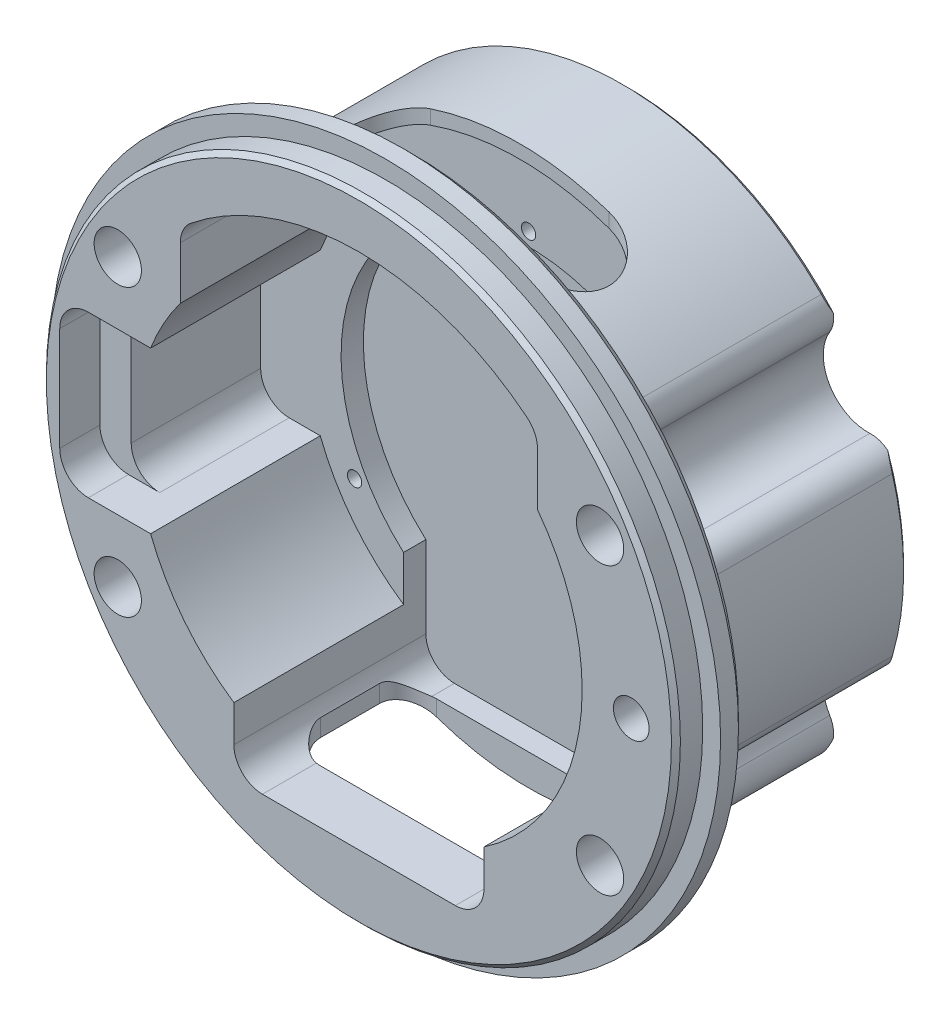
SolidWorks part; units mm, degrees
note: '?' marks a value the reader was unsure of.
material "6061-T6"
ref_plane "Plan de face" through (0, 0, 0) normal (0, 0, 1) x (1, 0, 0)
ref_plane "Plan de dessus" through (0, 0, 0) normal (0, 1, 0) x (1, 0, 0)
ref_plane "Plan de droite" through (0, 0, 0) normal (1, 0, 0) x (0, 0, -1)
ref_axis "X" through (-120.0359, 0, 0) along (1, 0, 0)?
ref_axis "Y" through (0, -123.4668, 0) along (0, 1, 0)?
ref_axis "Z" through (0, 0, 127.7992) along (0, 0, -1)?
sketch "Sketch1" plane through (0, 0, 0) normal (0, 0, 1) x (1, 0, 0)
  circle A0 centre (0, 0) radius 37.5
  dimension "D1" = 75
extrude "Boss-Extrude1" add sketch "Sketch1" along normal blind 27
sketch "Sketch2" plane through (0, 0, 27) normal (0, 0, 1) x (1, 0, 0)
  circle A0 centre (0, 0) radius 35.5
  dimension "D1" = 71
extrude "Boss-Extrude2" add sketch "Sketch2" along normal blind 3
sketch "Sketch13" plane through (0, 0, 0) normal (0, 0, -1) x (-1, 0, 0)
  circle A0 centre (0, 0) radius 31.5
  dimension "D1" = 63
extrude "Cut-Extrude2" cut sketch "Sketch13" against normal offset from surface (24 mm away) 3 flip side to cut up to face at (35.5, 0, 27)
hole_wizard "CBORE for M5 SHCS1" positions "Sketch3" profile "Sketch4" counterbore size "M5" standard "ANSI Metric" end condition through all
sketch "Sketch3" plane through (0, 0, 0) normal (0, 0, -1) x (-1, 0, 0)
  line L0 (0, 0) -> (47.1318, 0) construction
  line L1 (0, 0) -> (0, 39.9387) construction
  point P6 (-27, 16)
  point P8 (27, 16)
  point P9 (27, -16)
  point P10 (-27, -16)
  dimension "D1" = 54
  dimension "D2" = 32
sketch "Sketch4" plane through (27, -16, 0) normal (1, 0, 0) x (0, 1, 0)
  line L0 (0, 0) -> (0, 30)
  line L1 (0, 30) -> (2.65, 30)
  line L3 (2.65, 30) -> (2.65, 24)
  line L4 (2.65, 24) -> (5, 24)
  line L5 (5, 24) -> (5, 0)
  line L7 (5, 0) -> (0, 0)
  line L11 (0, -6.35) -> (0, 107.95) construction
  dimension "Thru Hole Dia." = 5.3
  dimension "Thru Hole Depth" = 30
  dimension "C'Bore Dia." = 10
  dimension "C'Bore Depth" = 24
hole_wizard "Ø4.0mm Dowel Hole1" positions "Sketch6" profile "Sketch7" hole size "Ø4.0" standard "ANSI Metric"
sketch "Sketch6" plane through (0, 0, 30) normal (0, 0, -1) x (-1, 0, 0)
  line L0 (0, 0) -> (49.9298, 0) construction
  line L1 (0, 0) -> (0, 44.2161) construction
  point P7 (-30.5, 0)
  dimension "D1" = 30.5
sketch "Sketch7" plane through (30.5, 0, 30) normal (1, 0, 0) x (0, -1, 0)
  line L0 (0, 0) -> (0, 6.2017)
  line L1 (0, 6.2017) -> (2, 5)
  line L2 (2, 5) -> (2, 0)
  line L5 (2, 0) -> (0, 0)
  line L10 (0, 6.2017) -> (-2, 5) construction
  line L11 (0, -6.35) -> (0, 107.95) construction
  dimension "Hole Dia." = 4
  dimension "Hole Depth" = 5
  dimension "Drill Angle" = 118
sketch "Sketch8" plane through (0, 0, 0) normal (0, 0, -1) x (-1, 0, 0)
  circle A0 centre (0, 0) radius 15.75
  dimension "D1" = 31.5
extrude "Cut-Extrude1" cut sketch "Sketch8" against normal blind 6.5
hole_wizard "M6x1.0 Tapped Hole1" positions "Sketch9" profile "Sketch10" tap size "M6x1.0" standard "ANSI Metric"
sketch "Sketch9" plane through (0, 0, 0) normal (0, 0, -1) x (-1, 0, 0)
  line L0 (0, 0) -> (0, 46.6913) construction
  line L1 (0, 0) -> (43.6542, 0) construction
  line L2 (0, 0) -> (-37.426, 37.426) construction
  circle A0 centre (0, 0) radius 25 construction
  point P14 (-17.6777, 17.6777)
  point P17 (17.6777, 17.6777)
  point P18 (17.6777, -17.6777)
  point P19 (-17.6777, -17.6777)
  dimension "D1" = 50
  dimension "D2" = 45
sketch "Sketch10" plane through (17.6777, -17.6777, 0) normal (1, 0, 0) x (0, 1, 0)
  line L0 (0, 0) -> (0, 9.5022)
  line L1 (0, 9.5022) -> (2.5, 8)
  line L2 (2.5, 8) -> (2.5, 0)
  line L5 (2.5, 0) -> (0, 0)
  line L10 (0, 9.5022) -> (-2.5, 8) construction
  line L11 (0, -6.35) -> (0, 107.95) construction
  dimension "Tap Drill Dia." = 5
  dimension "Tap Drill Depth" = 8
  dimension "Drill Angle" = 118
cosmetic thread "Hole Thread1" parameters "D1"=6, "D2"=6
cosmetic thread "Hole Thread2" parameters "D1"=6, "D2"=6
cosmetic thread "Hole Thread3" parameters "D1"=6, "D2"=6
cosmetic thread "Hole Thread4" parameters "D1"=6, "D2"=6
hole_wizard "Ø6.0mm Dowel Hole1" positions "Sketch11" profile "Sketch12" hole size "Ø6.0" standard "ANSI Metric"
sketch "Sketch11" plane through (0, 0, 0) normal (0, 0, -1) x (-1, 0, 0)
  line L0 (0, 0) -> (50.6513, 0) construction
  line L1 (0, 0) -> (0, 30.0462) construction
  circle A0 centre (0, 0) radius 25 construction
  point P13 (-25, 0)
  dimension "D1" = 50
sketch "Sketch12" plane through (25, 0, 0) normal (1, 0, 0) x (0, 1, 0)
  line L0 (0, 0) -> (0, 9.8026)
  line L1 (0, 9.8026) -> (3, 8)
  line L2 (3, 8) -> (3, 0)
  line L5 (3, 0) -> (0, 0)
  line L10 (0, 9.8026) -> (-3, 8) construction
  line L11 (0, -6.35) -> (0, 107.95) construction
  dimension "Hole Dia." = 6
  dimension "Hole Depth" = 8
  dimension "Drill Angle" = 118
chamfer "Chamfer1" distance 0.5 angle 45 1 edges at (35.5, 0, 30)
fillet "Fillet1" radius 3 8 edges at (-24.2118, 20.1504, 12) (-29.3017, 11.5613, 12) (-29.3017, -11.5613, 12) (-24.2118, -20.1504, 12) (24.2118, -20.1504, 12) (29.3017, -11.5613, 12) (29.3017, 11.5613, 12) (24.2118, 20.1504, 12)
chamfer "Chamfer2" distance 0.5 angle 45 4 edges at (-31.5, 0, 0) (0, 31.5, 0) (0, -31.5, 0) (31.5, 0, 0)
sketch "Sketch14" plane through (0, 0, 30) normal (0, 0, 1) x (1, 0, 0)
  circle A0 centre (0, 0) radius 25
  dimension "D1" = 50
extrude "Cut-Extrude3" [suppressed] cut sketch "Sketch14" against normal blind 8
chamfer "Chamfer3" distance 1 angle 45 1 edges at (37.5, 0, 24)
chamfer "Chamfer4" distance 0.5 angle 45 1 edges at (-15.75, 0, 0)
sketch "Sketch15" [suppressed] plane through (0, 0, 25.4) normal (0, 0, 1) x (1, 0, 0)
  line L1 (-18.3, 24) -> (18.3, 24)
  line L2 (-21.5, 20.8) -> (-21.5, -20.8)
  line L3 (-18.3, -24) -> (18.3, -24)
  line L4 (21.5, 20.8) -> (21.5, -20.8)
  line L5 (-21.5, 24) -> (21.5, -24) construction
  line L6 (-21.5, -24) -> (21.5, 24) construction
  arc A0 (-21.5, -20.8) -> (-18.3, -24) centre (-18.3, -20.8) ccw
  arc A1 (18.3, -24) -> (21.5, -20.8) centre (18.3, -20.8) ccw
  arc A2 (18.3, 24) -> (21.5, 20.8) centre (18.3, 20.8) cw
  arc A3 (-18.3, 24) -> (-21.5, 20.8) centre (-18.3, 20.8) ccw
  point P0 (0, 0)
  dimension "D1" = 3.2
  dimension "D2" = 43
  dimension "D3" = 48
extrude "Cut-Extrude4" [suppressed] cut sketch "Sketch15" against normal blind 14
sketch "Sketch20" [suppressed] plane through (0, 0, 11.4) normal (0, 0, 1) x (1, 0, 0)
  line L0 (0, 0) -> (0, 45.981) construction
  line L1 (18.3, 24) -> (-18.3, 24) construction
  line L2 (0, 0) -> (49.2522, 0) construction
  line L3 (-21.5, 20.8) -> (-21.5, -20.8) construction
  line L4 (-18.3, 24) -> (-11.9, 24)
  line L5 (-21.5, 14.6032) -> (-21.5, 20.8)
  line L6 (21.5, 14.6032) -> (21.5, 20.8)
  line L7 (18.3, 24) -> (11.9, 24)
  line L8 (18.3, -24) -> (11.9, -24)
  line L9 (21.5, -14.6032) -> (21.5, -20.8)
  line L10 (-21.5, -14.6032) -> (-21.5, -20.8)
  line L11 (-18.3, -24) -> (-11.9, -24)
  arc A0 (-18.4032, 17.6017) -> (-15.1, 20.8) centre (-18.3, 20.8) ccw
  arc A1 (-18.3, 24) -> (-21.5, 20.8) centre (-18.3, 20.8) ccw construction
  arc A2 (-11.9, 24) -> (-15.1, 20.8) centre (-11.9, 20.8) ccw
  arc A3 (-21.5, 14.6032) -> (-18.4032, 17.6017) centre (-18.5, 14.6032) cw
  arc A4 (-18.3, 24) -> (-21.5, 20.8) centre (-18.3, 20.8) ccw
  arc A5 (18.3, 24) -> (21.5, 20.8) centre (18.3, 20.8) cw
  arc A6 (21.5, 14.6032) -> (18.4032, 17.6017) centre (18.5, 14.6032) ccw
  arc A7 (11.9, 24) -> (15.1, 20.8) centre (11.9, 20.8) cw
  arc A8 (18.4032, 17.6017) -> (15.1, 20.8) centre (18.3, 20.8) cw
  arc A9 (18.4032, -17.6017) -> (15.1, -20.8) centre (18.3, -20.8) ccw
  arc A10 (11.9, -24) -> (15.1, -20.8) centre (11.9, -20.8) ccw
  arc A11 (21.5, -14.6032) -> (18.4032, -17.6017) centre (18.5, -14.6032) cw
  arc A12 (18.3, -24) -> (21.5, -20.8) centre (18.3, -20.8) ccw
  arc A13 (-18.3, -24) -> (-21.5, -20.8) centre (-18.3, -20.8) cw
  arc A14 (-21.5, -14.6032) -> (-18.4032, -17.6017) centre (-18.5, -14.6032) ccw
  arc A15 (-11.9, -24) -> (-15.1, -20.8) centre (-11.9, -20.8) cw
  arc A16 (-18.4032, -17.6017) -> (-15.1, -20.8) centre (-18.3, -20.8) cw
  dimension "D1" = 3.2
  dimension "D2" = 3
extrude "Boss-Extrude3" [suppressed] add sketch "Sketch20" along normal offset from surface (10 mm away) 4
sketch "Sketch16" [suppressed] plane through (0, 0, 0) normal (0, 0, -1) x (-1, 0, 0)
  line L0 (0, 0) -> (0, 13.623) construction
  line L1 (-14.5, -24) -> (14.5, -24)
  line L2 (-17.5, -27) -> (-17.5, -46)
  line L3 (-17.5, -46) -> (17.5, -46)
  line L4 (17.5, -27) -> (17.5, -46)
  arc A0 (14.5, -24) -> (17.5, -27) centre (14.5, -27) cw
  arc A1 (-14.5, -24) -> (-17.5, -27) centre (-14.5, -27) ccw
  point P7 (0, -24)
  point P10 (17.5, -24)
  dimension "D4" = 3
  dimension "D1" = 24
  dimension "D2" = 35
  dimension "D3" = 22
extrude "Cut-Extrude5" [suppressed] cut sketch "Sketch16" against normal offset from surface (20 mm away) 8
ref_plane "Plane1" [suppressed] through (0, -37.5, 0) normal (0, -1, 0) x (-1, 0, 0)
sketch "Sketch17" [suppressed] plane through (0, -37.5, 0) normal (0, -1, 0) x (-1, 0, 0)
  line L0 (0, 0) -> (0, -31.8118) construction
  line L1 (-10.5, -3.9) -> (10.5, -3.9)
  line L2 (-13.5, -6.9) -> (-13.5, -17.9)
  line L3 (-10.5, -20.9) -> (10.5, -20.9)
  line L4 (13.5, -6.9) -> (13.5, -17.9)
  line L5 (-37.5, -22.4) -> (37.5, -22.4) construction
  arc A0 (-13.5, -17.9) -> (-10.5, -20.9) centre (-10.5, -17.9) ccw
  arc A1 (10.5, -20.9) -> (13.5, -17.9) centre (10.5, -17.9) ccw
  arc A2 (10.5, -3.9) -> (13.5, -6.9) centre (10.5, -6.9) cw
  arc A3 (-10.5, -3.9) -> (-13.5, -6.9) centre (-10.5, -6.9) ccw
  point P7 (0, -3.9)
  point P16 (13.5, -3.9)
  point P19 (-13.5, -3.9)
  dimension "D4" = 3
  dimension "D1" = 27
  dimension "D2" = 1.5
  dimension "D3" = 17
extrude "Cut-Extrude6" [suppressed] cut sketch "Sketch17" against normal blind 20
sketch "Sketch18" [suppressed] plane through (0, -17.5, 0) normal (0, -1, 0) x (1, 0, 0)
  line L3 (-10.5, 7.9) -> (10.5, 7.9)
  line L4 (-10.5, 7.9) -> (10.5, 7.9)
  line L6 (-10.5, 20.9) -> (10.5, 20.9) construction
  line L7 (-13.5, 10.9) -> (-13.5, 17.9)
  line L8 (13.5, 17.9) -> (13.5, 10.9)
  line L9 (-10.5, 20.9) -> (10.5, 20.9)
  line L10 (13.5, 6.9) -> (13.5, 17.9) construction
  line L12 (-13.5, 17.9) -> (-13.5, 6.9) construction
  arc A0 (-10.5, 20.9) -> (-13.1263, 19.35) centre (-10.5, 17.9) ccw construction
  arc A2 (-10.5, 20.9) -> (-13.5, 17.9) centre (-10.5, 17.9) ccw
  arc A3 (13.5, 17.9) -> (10.5, 20.9) centre (10.5, 17.9) ccw
  arc A4 (-13.5, 10.9) -> (-10.5, 7.9) centre (-10.5, 10.9) ccw
  arc A5 (10.5, 7.9) -> (13.5, 10.9) centre (10.5, 10.9) ccw
  arc A6 (13.1263, 19.35) -> (10.5, 20.9) centre (10.5, 17.9) ccw construction
  arc A7 (-10.5, 20.9) -> (-13.1263, 19.35) centre (-10.5, 17.9) ccw construction
  dimension "D2" = 3
  dimension "D1" = 4
extrude "Cut-Extrude8" [suppressed] cut sketch "Sketch18" against normal blind 20
sketch "Sketch21" [suppressed] plane through (0, 0, 11.4) normal (0, 0, 1) x (1, 0, 0)
  line L0 (11.9, 24) -> (-11.9, 24) construction
  line L1 (-10.3, -24) -> (10.3, -24)
  line L2 (-13.5, -20.8) -> (-13.5, 20.8)
  line L3 (-10.3, 24) -> (10.3, 24)
  line L4 (13.5, -20.8) -> (13.5, 20.8)
  line L5 (-13.5, -24) -> (13.5, 24) construction
  line L6 (-13.5, 24) -> (13.5, -24) construction
  arc A0 (-10.3, -24) -> (-13.5, -20.8) centre (-10.3, -20.8) cw
  arc A1 (10.3, -24) -> (13.5, -20.8) centre (10.3, -20.8) ccw
  arc A2 (10.3, 24) -> (13.5, 20.8) centre (10.3, 20.8) cw
  arc A3 (-13.5, 20.8) -> (-10.3, 24) centre (-10.3, 20.8) cw
  point P0 (0, 0)
  dimension "D1" = 3.2
  dimension "D2" = 27
extrude "Cut-Extrude9" [suppressed] cut sketch "Sketch21" against normal blind 3.5
hole_wizard "M2x0.4 Tapped Hole1" [suppressed] positions "Sketch22" profile "Sketch23" tap size "M2x0.4" standard "ANSI Metric"
sketch "Sketch22" [suppressed] plane through (0, 0, 21.4) normal (0, 0, 1) x (1, 0, 0)
  line L0 (0, 0) -> (0, 50.1582) construction
  line L1 (0, 0) -> (52.8371, 0) construction
  point P0 (-19, 21)
  point P9 (19, 21)
  point P10 (19, -21)
  point P11 (-19, -21)
  dimension "D1" = 38
  dimension "D2" = 42
sketch "Sketch23" plane through (-19, 21, 21.4) normal (1, 0, 0) x (0, -1, 0)
  line L0 (0, 0) -> (0, 6.4807)
  line L1 (0, 6.4807) -> (0.8, 6)
  line L2 (0.8, 6) -> (0.8, 0)
  line L5 (0.8, 0) -> (0, 0)
  line L10 (0, 6.4807) -> (-0.8, 6) construction
  line L11 (0, -6.35) -> (0, 107.95) construction
  dimension "Tap Drill Dia." = 1.6
  dimension "Tap Drill Depth" = 6
  dimension "Drill Angle" = 118
cosmetic thread "Hole Thread5" [suppressed] parameters "D1"=4, "D2"=2
cosmetic thread "Hole Thread6" [suppressed] parameters "D1"=4, "D2"=2
cosmetic thread "Hole Thread7" [suppressed] parameters "D1"=4, "D2"=2
cosmetic thread "Hole Thread8" [suppressed] parameters "D1"=4, "D2"=2
sketch "Sketch24" [suppressed] plane through (0, 0, 25.4) normal (0, 0, 1) x (1, 0, 0)
  line L0 (21.5, -20.8) -> (21.5, 20.8) construction
  line L1 (-30.3, 9) -> (23.3, 9)
  line L2 (-33.5, 5.8) -> (-33.5, -5.8)
  line L3 (-30.3, -9) -> (23.3, -9)
  line L4 (26.5, 5.8) -> (26.5, -5.8)
  line L5 (-21.5, 20.8) -> (-21.5, -20.8) construction
  line L6 (0, 0) -> (-47.321, 0) construction
  line L7 (0, 0) -> (0, 45.7985) construction
  arc A0 (23.3, -9) -> (26.5, -5.8) centre (23.3, -5.8) ccw
  arc A1 (23.3, 9) -> (26.5, 5.8) centre (23.3, 5.8) cw
  arc A2 (-33.5, -5.8) -> (-30.3, -9) centre (-30.3, -5.8) ccw
  arc A3 (-30.3, 9) -> (-33.5, 5.8) centre (-30.3, 5.8) ccw
  point P11 (-33.5, 0)
  point P19 (-33.5, -9)
  point P22 (-33.5, 9)
  dimension "D4" = 3.2
  dimension "D1" = 5
  dimension "D2" = 12
  dimension "D3" = 18
extrude "Cut-Extrude10" [suppressed] cut sketch "Sketch24" against normal blind 5.5
sketch "Sketch25" plane through (0, 0, 30) normal (0, 0, 1) x (1, 0, 0)
  circle A0 centre (0, 0) radius 21
  dimension "D1" = 42
extrude "Cut-Extrude11" cut sketch "Sketch25" against normal blind 21.5
sketch "Sketch26" plane through (0, 0, 30) normal (0, 0, 1) x (1, 0, 0)
  line L0 (0, 0) -> (0, -50.047) construction
  line L2 (-10.8, 0) -> (10.8, 0)
  line L3 (-14, -3.2) -> (-14, -24.8)
  line L4 (-10.8, -28) -> (10.8, -28)
  line L5 (14, -3.2) -> (14, -24.8)
  line L6 (-14, 0) -> (14, -28) construction
  line L7 (-14, -28) -> (14, 0) construction
  arc A0 (-14, -24.8) -> (-10.8, -28) centre (-10.8, -24.8) ccw
  arc A1 (10.8, -28) -> (14, -24.8) centre (10.8, -24.8) ccw
  arc A2 (10.8, 0) -> (14, -3.2) centre (10.8, -3.2) cw
  arc A3 (-10.8, 0) -> (-14, -3.2) centre (-10.8, -3.2) ccw
  point P3 (0, -14)
  dimension "D1" = 3.2
  dimension "D2" = 28
  dimension "D3" = 28
extrude "Cut-Extrude12" cut sketch "Sketch26" against normal up to surface (21.5 mm away) up to face at (21, 0, 8.5)
sketch "Sketch27" plane through (0, 0, 0) normal (0, 0, -1) x (-1, 0, 0)
  line L0 (0, 0) -> (0, -46.9622) construction
  line L2 (-25, -44.5) -> (25, -44.5)
  line L3 (-25, -44.5) -> (-25, -24.5)
  line L4 (-25, -24.5) -> (25, -24.5)
  line L5 (25, -44.5) -> (25, -24.5)
  line L6 (-25, -44.5) -> (25, -24.5) construction
  line L7 (-25, -24.5) -> (25, -44.5) construction
  point P3 (0, -34.5)
  dimension "D1" = 50
  dimension "D2" = 24.5
  dimension "D3" = 20
extrude "Cut-Extrude13" [suppressed] cut sketch "Sketch27" against normal up to surface (24 mm away)
sketch "Sketch28" plane through (0, 0, 30) normal (0, 0, 1) x (1, 0, 0)
  line L0 (0, 0) -> (-49.6588, 0) construction
  line L2 (-6.3001, 9) -> (-30.3, 9)
  line L3 (-3.1001, 5.8) -> (-3.1001, -5.8)
  line L4 (-6.3001, -9) -> (-30.3, -9)
  line L5 (-33.5, 5.8) -> (-33.5, -5.8)
  line L6 (-3.1001, 9) -> (-33.5, -9) construction
  line L7 (-3.1001, -9) -> (-33.5, 9) construction
  arc A0 (-3.1001, -5.8) -> (-6.3001, -9) centre (-6.3001, -5.8) cw
  arc A1 (-6.3001, 9) -> (-3.1001, 5.8) centre (-6.3001, 5.8) cw
  arc A2 (-30.3, -9) -> (-33.5, -5.8) centre (-30.3, -5.8) cw
  arc A3 (-30.3, 9) -> (-33.5, 5.8) centre (-30.3, 5.8) ccw
  point P3 (-18.3001, 0)
  dimension "D1" = 3.2
  dimension "D2" = 33.5
  dimension "D3" = 18
extrude "Cut-Extrude14" cut sketch "Sketch28" against normal blind 4.5
sketch "Sketch29" plane through (0, 0, 30) normal (0, 0, 1) x (1, 0, 0)
  circle A0 centre (0, 0) radius 25
  dimension "D1" = 50
extrude "Cut-Extrude15" cut sketch "Sketch29" against normal offset from surface (19 mm away) 2.5 up to face at (0, -16.9297, 8.5)
sketch "Sketch30" plane through (0, 0, 25.5) normal (0, 0, 1) x (1, 0, 0)
  line L0 (-30.3, -9) -> (-23.3238, -9) construction
  line L1 (-23.3238, 9) -> (-30.3, 9) construction
  line L2 (-26.8, -9) -> (-23.3238, -9)
  line L3 (-23.3238, 9) -> (-26.8, 9)
  line L4 (-30, 5.8) -> (-30, -5.8)
  arc A0 (-23.3238, 9) -> (-23.3238, -9) centre (0, 0) ccw construction
  arc A1 (-23.3238, 9) -> (-23.3238, -9) centre (0, 0) ccw
  arc A2 (-30, -5.8) -> (-26.8, -9) centre (-26.8, -5.8) ccw
  arc A3 (-30, 5.8) -> (-26.8, 9) centre (-26.8, 5.8) cw
  dimension "D2" = 3.2
  dimension "D1" = 30
extrude "Cut-Extrude16" cut sketch "Sketch30" against normal up to surface (14.5 mm away) up to face at (0, 2.4088, 11)
hole_wizard "M2x0.4 Tapped Hole2" positions "Sketch31" profile "Sketch32" tap size "M2x0.4" standard "ANSI Metric"
sketch "Sketch31" plane through (0, 0, 11) normal (0, 0, 1) x (1, 0, 0)
  line L0 (0, 0) -> (0, 51.5847) construction
  line L1 (0, 0) -> (51.0764, 0) construction
  line L2 (0, 0) -> (47.2309, -27.2688) construction
  circle A0 centre (0, 0) radius 22.5 construction
  point P11 (0, 22.5)
  point P20 (19.4856, -11.25)
  point P23 (-19.4856, -11.25)
  dimension "D1" = 45
  dimension "D2" = 120
sketch "Sketch32" plane through (-19.4856, -11.25, 11) normal (1, 0, 0) x (0, -1, 0)
  line L0 (0, 0) -> (0, 5.6807)
  line L1 (0, 5.6807) -> (0.8, 5.2)
  line L2 (0.8, 5.2) -> (0.8, 0)
  line L5 (0.8, 0) -> (0, 0)
  line L10 (0, 5.6807) -> (-0.8, 5.2) construction
  line L11 (0, -6.35) -> (0, 107.95) construction
  dimension "Tap Drill Dia." = 1.6
  dimension "Tap Drill Depth" = 5.2
  dimension "Drill Angle" = 118
cosmetic thread "Hole Thread9" parameters "D1"=4, "D2"=2
cosmetic thread "Hole Thread10" parameters "D1"=4, "D2"=2
cosmetic thread "Hole Thread11" parameters "D1"=4, "D2"=2
sketch "Sketch33" [suppressed] plane through (0, 0, 9) normal (0, 0, 1) x (1, 0, 0)
  line L0 (14, -24.5) -> (-14, -24.5) construction
  line L1 (14, -24.5) -> (-14, -24.5)
  line L2 (10.8, -23.3) -> (-10.8, -23.3)
  line L3 (-14, -24.5) -> (-14, -15.6525) construction
  line L4 (14, -15.6525) -> (14, -24.5) construction
  line L5 (-14, -20.1) -> (-14, -24.5)
  line L6 (14, -24.5) -> (14, -20.1)
  line L7 (14, -23.3) -> (-14, -23.3) construction
  arc A0 (-10.8, -23.3) -> (-14, -20.1) centre (-10.8, -20.1) cw
  arc A1 (10.8, -23.3) -> (14, -20.1) centre (10.8, -20.1) ccw
  dimension "D2" = 3.2
  dimension "D1" = 1.2
extrude "Boss-Extrude4" [suppressed] add sketch "Sketch33" along normal blind 3.5
ref_plane "Plane2" through (0, 31.5, 0) normal (0, 1, 0) x (1, 0, 0)
sketch "Sketch34" plane through (0, 31.5, 0) normal (0, 1, 0) x (1, 0, 0)
  line L0 (0, 0) -> (0, -40.8469) construction
  line L1 (10, -17) -> (-10, -17) construction
  line L2 (10, -22) -> (-10, -22)
  line L3 (10, -12) -> (-10, -12)
  line L4 (23.1148, 0) -> (-23.1148, 0) construction
  arc A0 (10, -22) -> (10, -12) centre (10, -17) ccw
  arc A1 (-10, -12) -> (-10, -22) centre (-10, -17) ccw
  point P5 (0, -17)
  dimension "D1" = 10
  dimension "D2" = 30
  dimension "D3" = 17
extrude "Cut-Extrude17" cut sketch "Sketch34" against normal up to next
ref_plane "Plane3" through (0, -31.5, 0) normal (0, -1, 0) x (-1, 0, 0)
sketch "Sketch35" plane through (0, -31.5, 0) normal (0, -1, 0) x (-1, 0, 0)
  line L0 (0, 0) -> (0, -38.1665) construction
  line L1 (22.2805, -24) -> (-22.2805, -24) construction
  line L2 (-10.3, -11) -> (10.3, -11)
  line L3 (-13.5, -14.2) -> (-13.5, -20.8)
  line L4 (-10.3, -24) -> (10.3, -24)
  line L5 (13.5, -14.2) -> (13.5, -20.8)
  line L6 (-13.5, -11) -> (13.5, -24) construction
  line L7 (-13.5, -24) -> (13.5, -11) construction
  arc A0 (-13.5, -20.8) -> (-10.3, -24) centre (-10.3, -20.8) ccw
  arc A1 (10.3, -24) -> (13.5, -20.8) centre (10.3, -20.8) ccw
  arc A2 (10.3, -11) -> (13.5, -14.2) centre (10.3, -14.2) cw
  arc A3 (-10.3, -11) -> (-13.5, -14.2) centre (-10.3, -14.2) ccw
  point P3 (0, -17.5)
  dimension "D1" = 3.2
  dimension "D2" = 13
  dimension "D3" = 27
extrude "Cut-Extrude18" cut sketch "Sketch35" against normal up to next
sketch "Sketch36" plane through (0, 0, 30) normal (0, 0, 1) x (1, 0, 0)
  line L0 (20, 15) -> (20, 20.8806)
  line L1 (0, 0) -> (0, 49.5642) construction
  line L2 (-20, 15) -> (-20, 20.8806)
  arc A0 (18.806, 23.3738) -> (-18.806, 23.3738) centre (0, 0) ccw
  arc A1 (14, -20.7123) -> (-23.3238, 9) centre (0, 0) ccw construction
  arc A2 (20, 15) -> (-20, 15) centre (0, 0) ccw
  arc A3 (18.806, 23.3738) -> (20, 20.8806) centre (16.8, 20.8806) cw
  arc A4 (-18.806, 23.3738) -> (-20, 20.8806) centre (-16.8, 20.8806) ccw
  dimension "D1" = 3.2
  dimension "D2" = 30
  dimension "D3" = 40
extrude "Cut-Extrude19" cut sketch "Sketch36" against normal up to surface (19 mm away) up to face at (0.8, 22.5, 11)
equation "\"D3@Sketch7\" = \"D2@Sketch5\""
